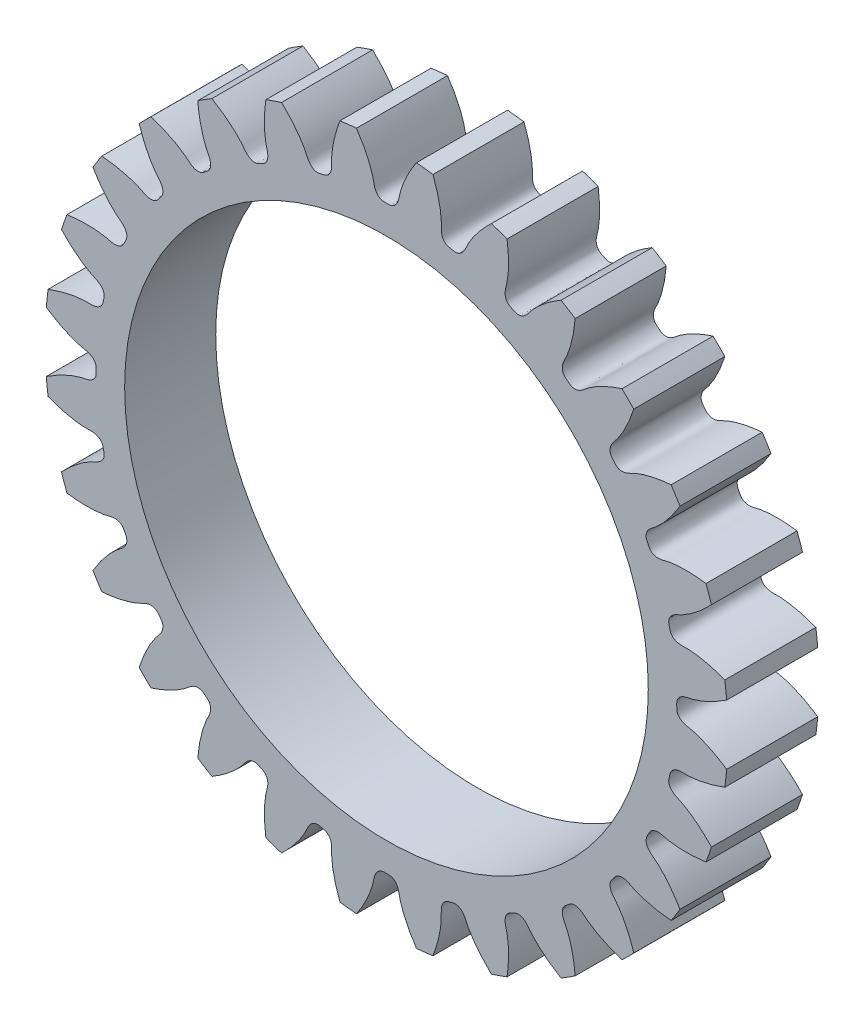
SolidWorks part; units mm, degrees
ref_plane "Front Plane" through (0, 0, 0) normal (0, 0, 1) x (1, 0, 0)
ref_plane "Top Plane" through (0, 0, 0) normal (0, 1, 0) x (1, 0, 0)
ref_plane "Right Plane" through (0, 0, 0) normal (1, 0, 0) x (0, 0, -1)
ref_axis "Axis1" through (0, 0, 55) along (0, 0, -1)
sketch "SketchRevolveSpurGear" plane through (0, 0, 0) normal (1, 0, 0) x (0, 0, -1)
  line L0 (0, 0) -> (1, 0) construction
  line L1 (-2, 0) -> (-2, 15)
  line L2 (-2, 15) -> (2, 15)
  line L3 (2, 15) -> (2, 0)
  line L4 (2, 0) -> (-2, 0)
  dimension "Side1" = 2
  dimension "OutsideRadius" = 15
  dimension "Side2" = 2
revolve "SpurGear" add sketch "SketchRevolveSpurGear" angle 360 about L0
sketch "SketchToothSpurGear" plane through (0, 0, 0) normal (0, 0, 1) x (1, 0, 0)
  arc A0 (14.9895, 1.3477) -> (14.9895, -1.3477) centre (0, 0) cw
  spline S0 degree 3 poles (14.9895, -1.3477) (14.8341, -1.2422) (14.6273, -1.1129) (14.3674, -0.9709) (14.2273, -0.8993) (14.0943, -0.836) (13.969, -0.7805) (13.8515, -0.7323) (13.7423, -0.6911) (13.6415, -0.6561) (13.5496, -0.6271) (13.4666, -0.6034) (13.3928, -0.5845) (13.2771, -0.5583) (13.1664, -0.541) (13.0647, -0.5056) (13.0146, -0.4844) (12.9658, -0.4588) (12.9179, -0.4274) (12.8704, -0.3877) (12.8245, -0.3364) (12.7835, -0.2698) (12.757, -0.1918) (12.7465, -0.0996) (12.752, 0) (12.7465, 0.0996) (12.757, 0.1918) (12.7835, 0.2698) (12.8245, 0.3364) (12.8704, 0.3877) (12.9179, 0.4274) (12.9658, 0.4588) (13.0146, 0.4844) (13.0647, 0.5056) (13.1664, 0.541) (13.2771, 0.5583) (13.3928, 0.5845) (13.4666, 0.6034) (13.5496, 0.6271) (13.6415, 0.6561) (13.7423, 0.6911) (13.8515, 0.7323) (13.969, 0.7805) (14.0943, 0.836) (14.2273, 0.8993) (14.3674, 0.9709) (14.6273, 1.1129) (14.8341, 1.2422) (14.9895, 1.3477) knots 0 0 0 0 0.101926 0.13223 0.160698 0.187329 0.212123 0.235081 0.256202 0.275487 0.292935 0.308546 0.322321 0.334259 0.372935 0.382829 0.392597 0.402447 0.412671 0.423662 0.43591 0.449896 0.465798 0.48017 0.5 0.51983 0.534202 0.550104 0.56409 0.576338 0.587329 0.597553 0.607403 0.617171 0.627065 0.665741 0.677679 0.691454 0.707065 0.724513 0.743798 0.764919 0.787877 0.812671 0.839302 0.86777 0.898074 1 1 1 1
extrude "ToothExtrudeCutSpurGear" cut sketch "SketchToothSpurGear" against normal blind 2 and the other way blind 2
pattern_circular "PatternSpurGear" count 28 every 12.857 about axis through (0, 0, 55) along (0, 0, -1) of "ToothExtrudeCutSpurGear"
sketch "BoreRevolveSketch" plane through (0, 0, 0) normal (1, 0, 0) x (0, 0, -1)
  line L0 (0, 0) -> (1, 0) construction
  line L1 (-2, 0) -> (2, 0)
  line L2 (2, 0) -> (2, 11.5)
  line L3 (2, 11.5) -> (-2, 11.5)
  line L4 (-2, 11.5) -> (-2, 0)
  dimension "BoreSide1" = 2
  dimension "TaperSide1" = 11.5
  dimension "BoreSide2" = 2
  dimension "TaperSide2" = 11.5
revolve "BoreRevolveCut" cut sketch "BoreRevolveSketch" angle 360 about L0
sketch "AuxiliarySketchSpurGear" plane through (0, 0, 0) normal (0, 0, 1) x (1, 0, 0)
  circle A0 centre (0, 0) radius 14 construction
  circle A1 centre (0, 0) radius 13.1557 construction
  circle A2 centre (0, 0) radius 13.2665 construction
  circle A3 centre (0, 0) radius 15 construction
  circle A4 centre (0, 0) radius 12.75 construction
  dimension "PitchDiameter" = 28
  dimension "BaseDiameter" = 26.3114
  dimension "FormDiameter" = 26.5329
  dimension "MajorDiameter" = 30
  dimension "MinorDiameter" = 25.5
